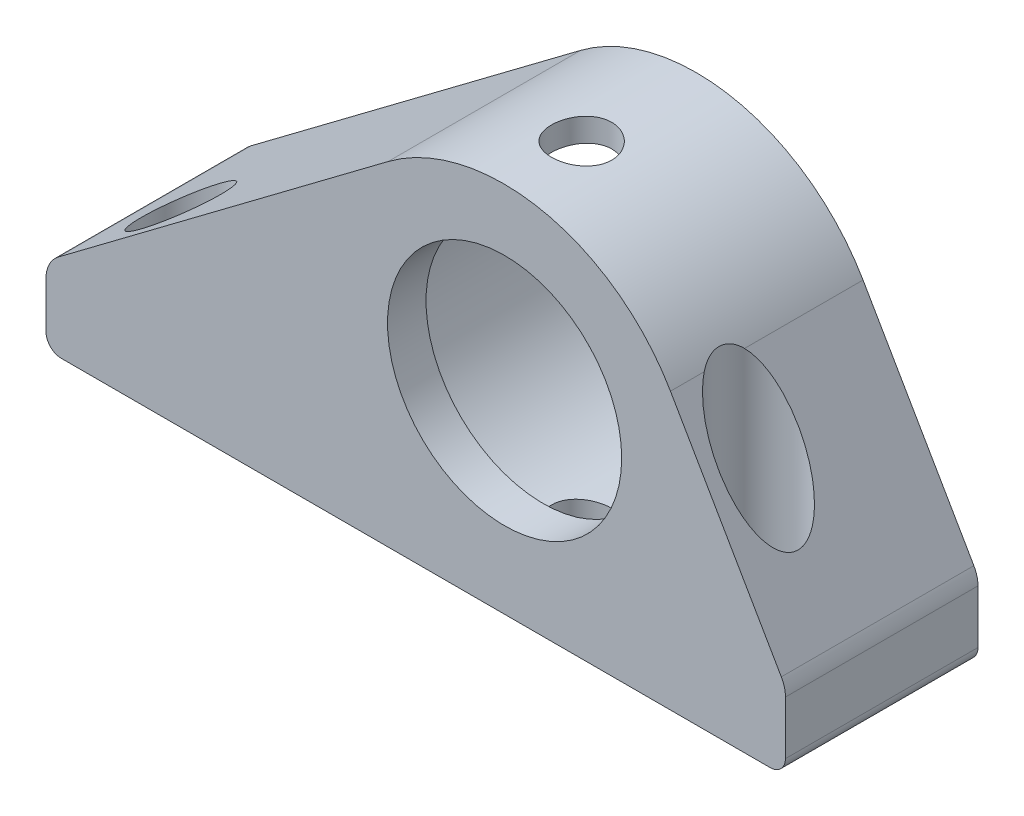
SolidWorks part; units mm, degrees
ref_plane "Alzado" through (0, 0, 0) normal (0, 0, 1) x (1, 0, 0)
ref_plane "Planta" through (0, 0, 0) normal (0, 1, 0) x (1, 0, 0)
ref_plane "Vista lateral" through (0, 0, 0) normal (1, 0, 0) x (0, 0, -1)
sketch "Croquis1" plane through (0, 0, 0) normal (0, 0, 1) x (1, 0, 0)
  line L4 (30.48, 0) -> (-30.48, 0)
  line L5 (-30.48, 0) -> (-30.48, 6.35)
  line L6 (-30.48, 6.35) -> (12.0465, 38.2778)
  line L7 (12.0465, 38.2778) -> (30.48, 6.35)
  line L8 (30.48, 6.35) -> (30.48, 0)
  line L9 (0, 0) -> (0, 44.0233) construction
  point P11 (0, 0)
  dimension "D1" = 6.35
  dimension "D2" = 38.2778
  dimension "D3" = 60.96
  dimension "D4" = 30
extrude "Saliente-Extruir1" add sketch "Croquis1" along normal blind 15.875
fillet "Redondeo1" radius 15.875 1 edges at (12.0465, 38.2778, 7.9375)
sketch "Croquis2" plane through (0, 0, 15.875) normal (0, 0, 1) x (1, 0, 0)
  line L0 (30.48, 6.35) -> (21.0022, 22.7661) construction
  circle A0 centre (7.3273, 15.9716) radius 9.652
  arc A1 (21.0022, 22.7661) -> (-2.2773, 27.5239) centre (7.254, 14.8286) ccw construction
  dimension "D1" = 5.08
  dimension "D2" = 19.304
  dimension "D3" = 15.24
extrude "Cortar-Extruir1" cut sketch "Croquis2" against normal up to next
sketch "Croquis3" plane through (0, 0, 15.875) normal (0, 0, 1) x (1, 0, 0)
  circle A0 centre (7.3273, 15.9716) radius 12.827
  dimension "D1" = 25.654
extrude "Cortar-Extruir2" cut sketch "Croquis3" against normal through all from offset 3.175 offset against normal yes
sketch "Croquis4" plane through (0, 0, 0) normal (0, -1, 0) x (1, 0, 0)
  line L0 (-30.48, 15.875) -> (-30.48, 0) construction
  line L1 (-30.48, 15.875) -> (30.48, 15.875) construction
  line L2 (0, 0) -> (0, 12.065) construction
  line L3 (-30.48, 0) -> (30.48, 0) construction
  line L4 (16.9793, 15.875) -> (-2.3247, 15.875) construction
  line L5 (16.9793, 15.875) -> (-2.3247, 15.875)
  circle A0 centre (-23.8125, 11.43) radius 3.2639
  circle A1 centre (23.8125, 11.43) radius 3.2639
  circle A3 centre (7.3273, 9.525) radius 2.4892
  point P21 (7.3273, 15.875)
  dimension "D1" = 6.5278
  dimension "D4" = 4.9784
  dimension "D5" = 6.35
  dimension "D2" = 6.6675
  dimension "D3" = 4.445
extrude "Cortar-Extruir3" cut sketch "Croquis4" against normal through all contours A3 | A0 | A1
fillet "Redondeo2" radius 1.27 2 edges at (30.48, 0, 7.9375) (-30.48, 0, 7.9375)
fillet "Redondeo3" radius 2.54 2 edges at (30.48, 6.35, 7.9375) (-30.48, 6.35, 7.9375)
